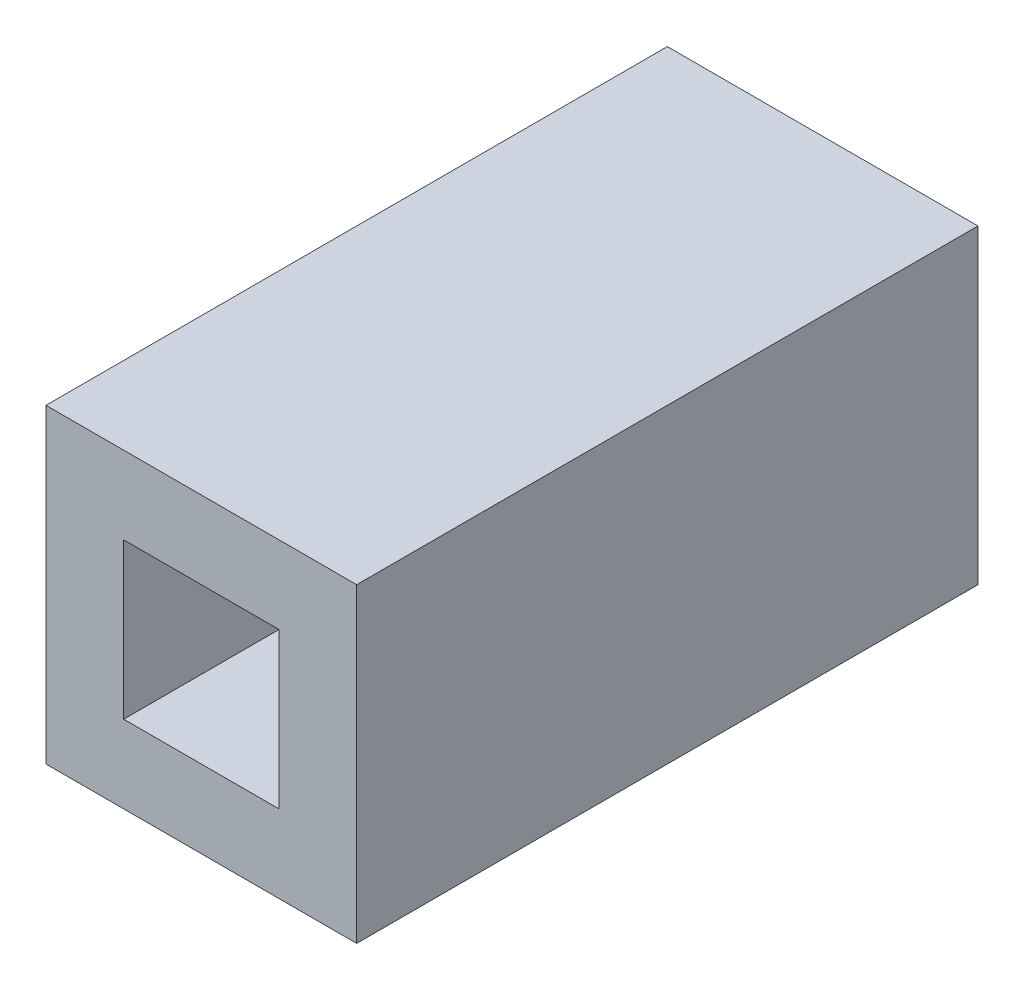
SolidWorks part; units mm, degrees
ref_plane "Front Plane" through (0, 0, 0) normal (0, 0, 1) x (1, 0, 0)
ref_plane "Top Plane" through (0, 0, 0) normal (0, 1, 0) x (1, 0, 0)
ref_plane "Right Plane" through (0, 0, 0) normal (1, 0, 0) x (0, 0, -1)
sketch "Sketch1" plane through (0, 0, 0) normal (0, 0, 1) x (1, 0, 0)
  line L1 (0, 0) -> (-25.4, 0)
  line L2 (0, 0) -> (0, 25.4)
  line L3 (0, 25.4) -> (-25.4, 25.4)
  line L4 (-25.4, 0) -> (-25.4, 25.4)
  line L5 (-19.05, 19.05) -> (-6.35, 19.05)
  line L6 (-19.05, 19.05) -> (-19.05, 6.35)
  line L7 (-19.05, 6.35) -> (-6.35, 6.35)
  line L8 (-6.35, 19.05) -> (-6.35, 6.35)
  dimension "D1" = 25.4
  dimension "D2" = 25.4
  dimension "D3" = 6.35
  dimension "D4" = 6.35
  dimension "D5" = 6.35
  dimension "D6" = 6.35
extrude "Boss-Extrude1" add sketch "Sketch1" along normal blind 50.8
